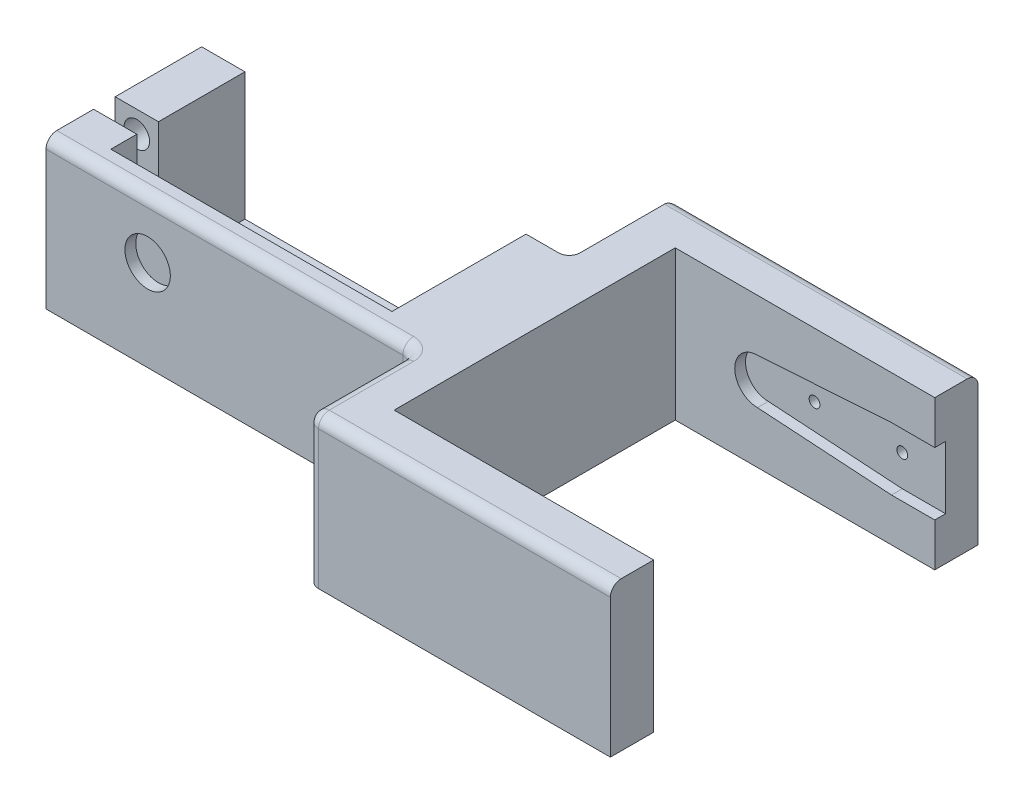
SolidWorks part; units mm, degrees
ref_plane "Front Plane" through (0, 0, 0) normal (0, 0, 1) x (1, 0, 0)
ref_plane "Top Plane" through (0, 0, 0) normal (0, 1, 0) x (1, 0, 0)
ref_plane "Right Plane" through (0, 0, 0) normal (1, 0, 0) x (0, 0, -1)
sketch "Sketch1" plane through (0, 0, 0) normal (0, 0, 1) x (1, 0, 0)
  line L1 (-37.5, -8.5) -> (37.5, -8.5) construction
  line L2 (-37.5, -8.5) -> (-37.5, 8.5) construction
  line L3 (-37.5, 8.5) -> (37.5, 8.5) construction
  line L4 (37.5, -8.5) -> (37.5, 8.5) construction
  line L5 (-37.5, -8.5) -> (37.5, 8.5) construction
  line L6 (-37.5, 8.5) -> (37.5, -8.5) construction
  line L7 (-42.5, 13.5) -> (-32.5, 13.5)
  line L8 (-42.5, 13.5) -> (-42.5, -16)
  line L9 (-42.5, -16) -> (-32.5, -16)
  line L10 (-32.5, 13.5) -> (-32.5, -16)
  line L11 (32.5, 13.5) -> (42.5, 13.5)
  line L12 (32.5, 13.5) -> (32.5, -16)
  line L13 (32.5, -16) -> (42.5, -16)
  line L14 (42.5, 13.5) -> (42.5, -16)
  line L15 (-42.5, -16) -> (42.5, -16)
  line L16 (-42.5, -16) -> (-42.5, -21)
  line L17 (-42.5, -21) -> (42.5, -21)
  line L18 (42.5, -16) -> (42.5, -21)
  circle A0 centre (-37.5, 8.5) radius 2.95
  circle A1 centre (37.5, 8.5) radius 2.95
  circle A2 centre (-37.5, -8.5) radius 2.95
  circle A3 centre (37.5, -8.5) radius 2.95
  point P0 (0, 0)
  point P19 (-37.5, 13.5)
  point P21 (37.5, 13.5)
  dimension "D1" = 5.9
  dimension "D2" = 17
  dimension "D3" = 75
  dimension "D4" = 10
  dimension "D5" = 5
  dimension "D6" = 7.5
  dimension "D7" = 5
extrude "Boss-Extrude1" add sketch "Sketch1" along normal mid plane 31 contours L10 L7 L8 L9 A2 A0 | L18 L13 L15 L9 L16 L17 | L14 L11 L12 L13 A3 A1 region at (-37.5, -1.5344, 0) region at (0, -18.5, 0) region at (37.5, -1.5344, 0)
sketch "Sketch2" plane through (0, 0, 15.5) normal (0, 0, 1) x (1, 0, 0)
  line L1 (-42.5, -21) -> (42.5, -21)
  line L2 (-42.5, -21) -> (-42.5, 13.5)
  line L3 (-42.5, 13.5) -> (42.5, 13.5)
  line L4 (42.5, -21) -> (42.5, 13.5)
  circle A0 centre (-19, 0) radius 1.6 construction
  circle A1 centre (-19, 0) radius 1.6 construction
  circle A2 centre (-19, 0) radius 5.25
  dimension "D1" = 10.5
extrude "Boss-Extrude2" add sketch "Sketch2" along normal blind 5
sketch "Sketch4" plane through (42.5, 0, 0) normal (1, 0, 0) x (0, 0, -1)
  line L0 (-20.5, 13.5) -> (15.5, 13.5) construction
  line L1 (-45, -21) -> (40, -21)
  line L2 (-45, -21) -> (-45, 13.5)
  line L3 (-45, 13.5) -> (40, 13.5)
  line L4 (40, -21) -> (40, 13.5)
  line L5 (-45, -21) -> (40, 13.5) construction
  line L6 (-45, 13.5) -> (40, -21) construction
  line L7 (-20.5, -21) -> (15.5, -21) construction
  line L8 (15.5, -3.75) -> (40, -3.75) construction
  line L9 (15.5, 13.5) -> (15.5, -21) construction
  line L10 (-45, -3.75) -> (-20.5, -3.75) construction
  line L11 (-20.5, -21) -> (-20.5, 13.5) construction
  point P0 (-2.5, -3.75)
  dimension "D1" = 85
extrude "Boss-Extrude3" add sketch "Sketch4" along normal blind 10
sketch "Sketch5" plane through (52.5, 0, 0) normal (1, 0, 0) x (0, 0, -1)
  line L0 (-45, -21) -> (40, -21) construction
  line L1 (-45, 13.5) -> (-35, 13.5)
  line L2 (-45, 13.5) -> (-45, -21)
  line L3 (-45, -21) -> (-35, -21)
  line L4 (-35, 13.5) -> (-35, -21)
  line L6 (40, 13.5) -> (30, 13.5)
  line L7 (40, 13.5) -> (40, -21)
  line L8 (40, -21) -> (30, -21)
  line L9 (30, 13.5) -> (30, -21)
  dimension "D1" = 10
extrude "Boss-Extrude4" add sketch "Sketch5" along normal blind 60
sketch "Sketch6" plane through (0, 0, 35) normal (0, 0, -1) x (-1, 0, 0)
  line L0 (-112.5, -3.75) -> (-102.5, -3.75) construction
  line L1 (-112.5, -21) -> (-112.5, 13.5) construction
  circle A0 centre (-102.5, -3.75) radius 5
  dimension "D1" = 10
  dimension "D2" = 10
extrude "Boss-Extrude5" add sketch "Sketch6" along normal blind 5
sketch "Sketch8" plane through (0, 0, -30) normal (0, 0, 1) x (1, 0, 0)
  line L1 (71.5, 1.5) -> (102.5, 3.5)
  line L6 (102.5, -11) -> (112.5, -11)
  line L7 (71.5, -9) -> (102.5, -11)
  line L8 (112.5, 13.5) -> (112.5, -21) construction
  line L9 (102.5, 3.5) -> (112.5, 3.5)
  line L10 (112.5, 3.5) -> (112.5, -11)
  circle A0 centre (102.5, -3.75) radius 5.65 construction
  circle A1 centre (102.5, -3.75) radius 5.65 construction
  circle A6 centre (71.5, -3.75) radius 5.25
  circle A11 centre (102.5, -3.75) radius 7.25
  line M9 (112.5, -21) -> (112.5, 13.5)
  dimension "D5" = 14.5
  dimension "D1" = 10.5
  dimension "D8" = 31
extrude "Cut-Extrude2" cut sketch "Sketch8" against normal blind 2.5 contours A1 | A11 L6 L9 M9 | L1 A11 L7 | A11 L1 A6 L7 | A6 region at (86.5013, -3.75, -30) region at (71.5, -3.75, -30) region at (102.5001, -3.75, -30) region at (110.043, -3.75, -30)
sketch "Sketch10" plane through (-42.5, 0, 0) normal (-1, 0, 0) x (0, 0, 1)
  line L0 (20.5, -21) -> (20.5, 13.5) construction
  line L1 (4.5, 13.5) -> (9.5, 13.5)
  line L2 (4.5, 13.5) -> (4.5, -5)
  line L3 (4.5, -5) -> (9.5, -5)
  line L4 (9.5, 13.5) -> (9.5, -5)
  line L5 (20.5, -21) -> (-15.5, -21) construction
  line L6 (20.5, 13.5) -> (-15.5, 13.5) construction
  dimension "D2" = 5
  dimension "D3" = 11
  dimension "D4" = 16
extrude "Cut-Extrude4" cut sketch "Sketch10" against normal up to surface (10 mm away) up to face at (-32.5, -1.25, 0)
sketch "Sketch11" plane through (0, 0, -40) normal (0, 0, -1) x (-1, 0, 0)
  circle A0 centre (-82.2, -3.75) radius 4.856
  circle A1 centre (-102.5, -3.75) radius 5
  circle A2 centre (-102.5, -3.75) radius 5
  dimension "D2" = 20.3
  dimension "D1" = 0
sketch "Sketch12" plane through (0, 0, -40) normal (0, 0, -1) x (-1, 0, 0)
  point P0 (-82.2, -3.75)
  point P3 (-102.5, -3.75)
hole_wizard "Ø2.5mm Dowel Hole1" positions "Sketch12" profile "Sketch13" hole size "Ø2.5" standard "ANSI Metric"
sketch "Sketch13" plane through (82.2, -3.75, -40) normal (1, 0, 0) x (0, 1, 0)
  line L0 (0, 0) -> (0, 10.7511)
  line L1 (0, 10.7511) -> (1.25, 10)
  line L2 (1.25, 10) -> (1.25, 0)
  line L5 (1.25, 0) -> (0, 0)
  line L10 (0, 10.7511) -> (-1.25, 10) construction
  line L11 (0, -6.35) -> (0, 107.95) construction
  dimension "Hole Dia." = 2.5
  dimension "Hole Depth" = 10
  dimension "Drill Angle" = 118
fillet "Fillet1" radius 2.5 8 edges at (42.5, 13.5, 32.75) (42.5, -3.75, 20.5) (42.5, -3.75, -15.5) (0, 13.5, 20.5) (77.5, 13.5, 45) (77.5, 13.5, -40) (42.5, -3.75, 45) (42.5, -3.75, -40)
sketch "Sketch14" plane through (0, 0, 15.5) normal (0, 0, -1) x (-1, 0, 0)
  circle A0 centre (19, 0) radius 5.25 construction
  circle A1 centre (19, 0) radius 5.25
extrude "Boss-Extrude6" add sketch "Sketch14" against normal blind 2.5
